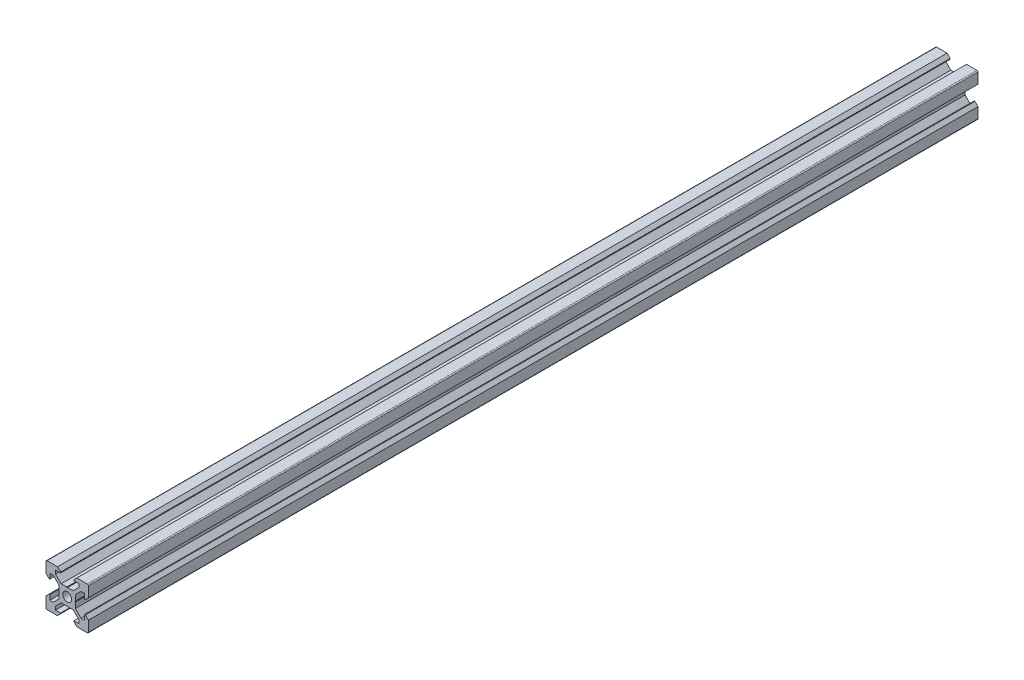
SolidWorks part; units mm, degrees
material "6061-T6 (SS)"
ref_plane "Front Plane" through (0, 0, 0) normal (0, 0, 1) x (1, 0, 0)
ref_plane "Top Plane" through (0, 0, 0) normal (0, 1, 0) x (1, 0, 0)
ref_plane "Right Plane" through (0, 0, 0) normal (1, 0, 0) x (0, 0, -1)
sketch "Sketch1" plane through (0, 0, 0) normal (0, 0, 1) x (1, 0, 0)
  line L1 (9.5, -10) -> (-9.5, -10)
  line L2 (10, -9.5) -> (10, 9.5)
  line L3 (9.5, 10) -> (-9.5, 10)
  line L4 (-10, -9.5) -> (-10, 9.5)
  line L5 (10, -10) -> (-10, 10) construction
  line L6 (10, 10) -> (-10, -10) construction
  circle A0 centre (0, 0) radius 2.1
  arc A1 (-9.5, 10) -> (-10, 9.5) centre (-9.5, 9.5) ccw
  arc A2 (10, 9.5) -> (9.5, 10) centre (9.5, 9.5) ccw
  arc A3 (9.5, -10) -> (10, -9.5) centre (9.5, -9.5) ccw
  arc A4 (-9.5, -10) -> (-10, -9.5) centre (-9.5, -9.5) cw
  point P0 (0, 0)
  line B0 (0, 0) -> (0, 10) construction
  line B1 (0, 3.69) -> (-0.21, 3.9)
  line B2 (-0.21, 3.9) -> (-2.8393, 3.9)
  line B3 (-2.8393, 3.9) -> (-5.5, 6.5607)
  line B4 (-5.5, 6.5607) -> (-5.5, 8.2)
  line B5 (-5.5, 8.2) -> (-3.125, 8.2)
  line B6 (-3.125, 8.2) -> (-3.125, 8.545)
  line B7 (-3.125, 8.545) -> (-4.58, 10)
  line B8 (-4.58, 10) -> (4.58, 10)
  line B9 (0, 0) -> (-5.9132, 5.9132) construction
  line B10 (3.125, 8.545) -> (4.58, 10)
  line B11 (3.125, 8.2) -> (3.125, 8.545)
  line B12 (5.5, 8.2) -> (3.125, 8.2)
  line B13 (5.5, 6.5607) -> (5.5, 8.2)
  line B14 (2.8393, 3.9) -> (5.5, 6.5607)
  line B15 (0.21, 3.9) -> (2.8393, 3.9)
  line B16 (0, 3.69) -> (0.21, 3.9)
  line B17 (0, 0) -> (-10, 0) construction
  line B18 (-3.69, 0) -> (-3.9, -0.21)
  line B19 (-3.9, -0.21) -> (-3.9, -2.8393)
  line B20 (-3.9, -2.8393) -> (-6.5607, -5.5)
  line B21 (-6.5607, -5.5) -> (-8.2, -5.5)
  line B22 (-8.2, -5.5) -> (-8.2, -3.125)
  line B23 (-8.2, -3.125) -> (-8.545, -3.125)
  line B24 (-8.545, -3.125) -> (-10, -4.58)
  line B25 (-10, -4.58) -> (-10, 4.58)
  line B26 (0, 0) -> (-5.9132, -5.9132) construction
  line B27 (-8.545, 3.125) -> (-10, 4.58)
  line B28 (-8.2, 3.125) -> (-8.545, 3.125)
  line B29 (-8.2, 5.5) -> (-8.2, 3.125)
  line B30 (-6.5607, 5.5) -> (-8.2, 5.5)
  line B31 (-3.9, 2.8393) -> (-6.5607, 5.5)
  line B32 (-3.9, 0.21) -> (-3.9, 2.8393)
  line B33 (-3.69, 0) -> (-3.9, 0.21)
  line B34 (0, 0) -> (0, -10) construction
  line B35 (0, -3.69) -> (0.21, -3.9)
  line B36 (0.21, -3.9) -> (2.8393, -3.9)
  line B37 (2.8393, -3.9) -> (5.5, -6.5607)
  line B38 (5.5, -6.5607) -> (5.5, -8.2)
  line B39 (5.5, -8.2) -> (3.125, -8.2)
  line B40 (3.125, -8.2) -> (3.125, -8.545)
  line B41 (3.125, -8.545) -> (4.58, -10)
  line B42 (4.58, -10) -> (-4.58, -10)
  line B43 (0, 0) -> (5.9132, -5.9132) construction
  line B44 (-3.125, -8.545) -> (-4.58, -10)
  line B45 (-3.125, -8.2) -> (-3.125, -8.545)
  line B46 (-5.5, -8.2) -> (-3.125, -8.2)
  line B47 (-5.5, -6.5607) -> (-5.5, -8.2)
  line B48 (-2.8393, -3.9) -> (-5.5, -6.5607)
  line B49 (-0.21, -3.9) -> (-2.8393, -3.9)
  line B50 (0, -3.69) -> (-0.21, -3.9)
  line B51 (0, 0) -> (10, 0) construction
  line B52 (3.69, 0) -> (3.9, 0.21)
  line B53 (3.9, 0.21) -> (3.9, 2.8393)
  line B54 (3.9, 2.8393) -> (6.5607, 5.5)
  line B55 (6.5607, 5.5) -> (8.2, 5.5)
  line B56 (8.2, 5.5) -> (8.2, 3.125)
  line B57 (8.2, 3.125) -> (8.545, 3.125)
  line B58 (8.545, 3.125) -> (10, 4.58)
  line B59 (10, 4.58) -> (10, -4.58)
  line B60 (0, 0) -> (5.9132, 5.9132) construction
  line B61 (8.545, -3.125) -> (10, -4.58)
  line B62 (8.2, -3.125) -> (8.545, -3.125)
  line B63 (8.2, -5.5) -> (8.2, -3.125)
  line B64 (6.5607, -5.5) -> (8.2, -5.5)
  line B65 (3.9, -2.8393) -> (6.5607, -5.5)
  line B66 (3.9, -0.21) -> (3.9, -2.8393)
  line B67 (3.69, 0) -> (3.9, -0.21)
  dimension "D1" = 4.2
  dimension "D2" = 20
sketch_block_instance "V Slot 1-4"
sketch_block "V Slot 1" parameters "D1"=10, "D2"=11, "D3"=4.3, "D4"=1.8, "D5"=0.21, "D6"=45, "D7"=9.16, "D8"=1.5, "D9"=6.25
sketch_block_instance "V Slot 1-5"
sketch_block_instance "V Slot 1-6"
sketch_block_instance "V Slot 1-7" parameters "D1"=31.2546, "D3"=0.5, "D2"=9.6469
extrude "Boss-Extrude1" add sketch "Sketch1" along normal mid plane 420 contours B67 B52 B53 B54 B55 B56 B57 B58 L2 A2 L3 B10 B11 B12 B13 B14 B15 B16 B1 B2 B3 B4 B5 B6 B7 A1 L4 B27 B28 B29 B30 B31 B32 B33 B18 B19 B20 B21 B22 B23 B24 A4 L1 B44 B45 B46 B47 B48 B49 region at (7.04, -9.7172, 0)
